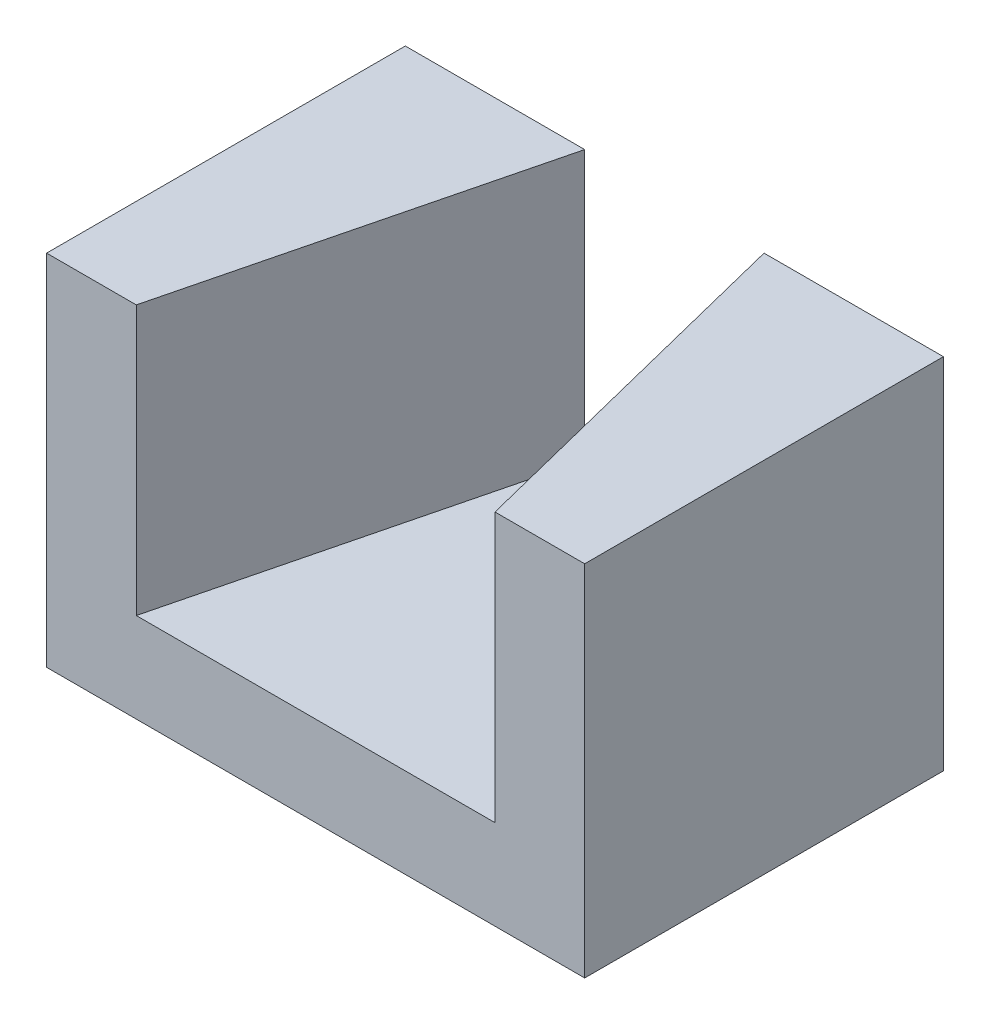
SolidWorks part; units mm, degrees
ref_plane "前基準面" through (0, 0, 0) normal (0, 0, 1) x (1, 0, 0)
ref_plane "上基準面" through (0, 0, 0) normal (0, 1, 0) x (1, 0, 0)
ref_plane "右基準面" through (0, 0, 0) normal (1, 0, 0) x (0, 0, -1)
sketch "草圖1" plane through (0, 0, 0) normal (0, 1, 0) x (1, 0, 0)
  line L0 (10, 0) -> (20, 40)
  line L1 (0, 0) -> (60, 0)
  line L2 (0, 0) -> (0, 40)
  line L3 (0, 40) -> (60, 40)
  line L6 (60, 0) -> (60, 40)
  line L7 (50, 0) -> (40, 40)
  dimension "D1" = 10
  dimension "D2" = 40
  dimension "D3" = 20
  dimension "D4" = 10
  dimension "D5" = 20
  dimension "D6" = 40
  dimension "D7" = 60
extrude "填料-伸長4" add sketch "草圖1" against normal blind 10 contours L1 L7 L3 L0 | L3 L2 L1 L0 | L7 L1 L6 L3 region at (7.7778, 0, -22.2222) region at (30, 0, -17.7778) region at (52.2222, 0, -22.2222)
extrude "填料-伸長5" add sketch "草圖1<7>" along normal blind 30 contours L3 L2 L1 L0 | L7 L1 L6 L3 region at (7.7778, 0, -22.2222) region at (52.2222, 0, -22.2222)
sketch "草圖1<7>" plane through (0, 0, 0) normal (0, 1, 0) x (1, 0, 0) same geometry as "草圖1"
